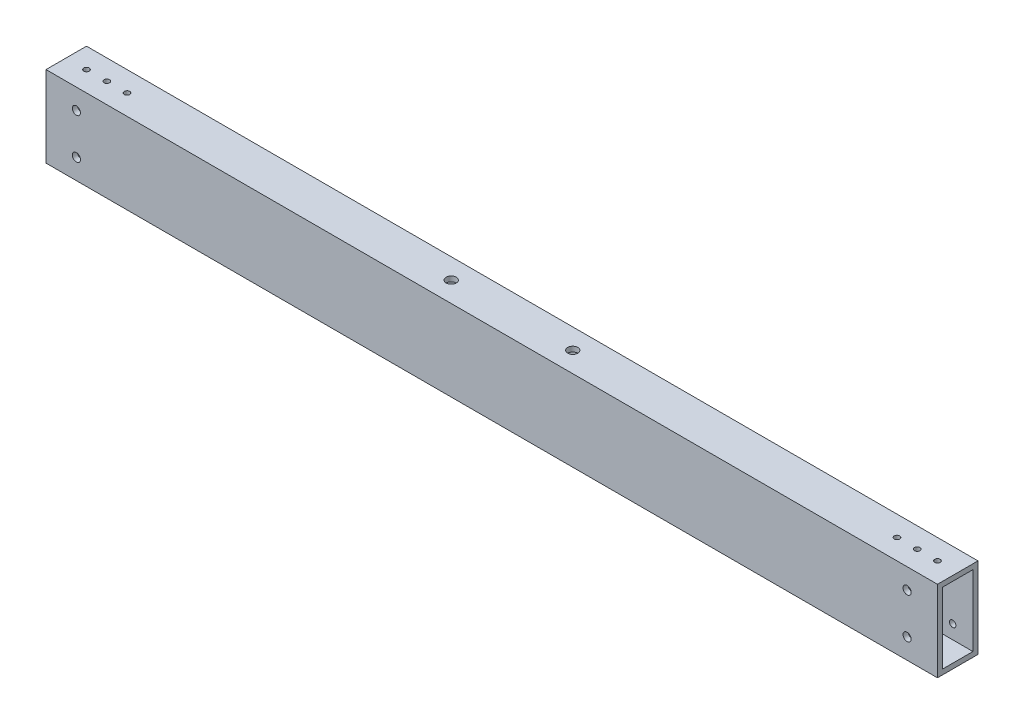
SolidWorks part; units mm, degrees
material "6061-T6 (SS)"
ref_plane "Front Plane" through (0, 0, 0) normal (0, 0, 1) x (1, 0, 0)
ref_plane "Top Plane" through (0, 0, 0) normal (0, 1, 0) x (1, 0, 0)
ref_plane "Right Plane" through (0, 0, 0) normal (1, 0, 0) x (0, 0, -1)
sketch "Sketch1" plane through (0, 0, 0) normal (0, 0, 1) x (1, 0, 0)
  line L1 (-279.4, 25.4) -> (279.4, 25.4)
  line L2 (-279.4, 25.4) -> (-279.4, -25.4)
  line L3 (-279.4, -25.4) -> (279.4, -25.4)
  line L4 (279.4, 25.4) -> (279.4, -25.4)
  line L5 (-279.4, 25.4) -> (279.4, -25.4) construction
  line L6 (-279.4, -25.4) -> (279.4, 25.4) construction
  point P0 (0, 0)
  dimension "D1" = 50.8
  dimension "D2" = 558.8
extrude "Boss-Extrude1" add sketch "Sketch1" along normal mid plane 25.4
sketch "Sketch2" plane through (279.4, 0, 0) normal (1, 0, 0) x (0, 0, -1)
  line L8 (9.525, -22.225) -> (9.525, 22.225)
  line L9 (9.525, 22.225) -> (-9.525, 22.225)
  line L10 (-9.525, 22.225) -> (-9.525, -22.225)
  line L11 (-9.525, -22.225) -> (9.525, -22.225)
  line L12 (9.525, -22.225) -> (9.525, 22.225)
  line L13 (9.525, 22.225) -> (-9.525, 22.225)
  line L14 (-9.525, 22.225) -> (-9.525, -22.225)
  line L15 (-9.525, -22.225) -> (9.525, -22.225)
  dimension "D1" = 3.175
extrude "Cut-Extrude1" cut sketch "Sketch2" against normal through all
sketch "Sketch3" plane through (0, 0, 12.7) normal (0, 0, 1) x (1, 0, 0)
sketch "Sketch4" plane through (0, 25.4, 0) normal (0, 1, 0) x (1, 0, 0)
  line L0 (-279.4, -12.7) -> (-279.4, 12.7) construction
  line L1 (0, -12.7) -> (0, 12.7) construction
  line L2 (279.4, -12.7) -> (-279.4, -12.7) construction
  line L3 (279.4, 12.7) -> (-279.4, 12.7) construction
  circle A0 centre (-304.8, 0) radius 1.7272
  circle A1 centre (-292.1, 0) radius 1.7272
  circle A3 centre (-266.7, 0) radius 1.7272
  circle A4 centre (-254, 0) radius 1.7272
  circle A5 centre (-241.3, 0) radius 1.7272
  circle A7 centre (241.3, 0) radius 1.7272
  circle A8 centre (254, 0) radius 1.7272
  circle A9 centre (266.7, 0) radius 1.7272
  circle A12 centre (-279.4, 0) radius 1.7272 [skipped]
  circle A14 centre (-228.6, 0) radius 1.7272 [skipped]
  dimension "D2" = 3.4544
  dimension "D3" = 7
  dimension "D4" = 12.7
extrude "Cut-Extrude2" cut sketch "Sketch4" against normal blind 6.35
hole_wizard "1/4-20 Tapped Hole1" positions "Sketch8" profile "Sketch7" tap size "1/4-20" standard "ANSI Inch"
sketch "Sketch8" plane through (0, 0, 12.7) normal (0, 0, 1) x (1, 0, 0)
  line L0 (-279.4, 25.4) -> (-279.4, -25.4) construction
  line L1 (279.4, -25.4) -> (279.4, 25.4) construction
  line L2 (-279.4, -25.4) -> (279.4, -25.4) construction
  point P0 (-260.35, 12.7)
  point P2 (-260.35, -12.7)
  point P4 (260.35, 12.7)
  point P6 (260.35, -12.7)
  dimension "D1" = 25.4
  dimension "D2" = 19.05
  dimension "D3" = 25.4
  dimension "D4" = 19.05
  dimension "D5" = 12.7
  dimension "D6" = 12.7
sketch "Sketch7" plane through (-260.35, 12.7, 12.7) normal (1, 0, 0) x (0, -1, 0)
  line L0 (0, 0) -> (0, 6.6138)
  line L1 (0, 6.6138) -> (2.5527, 5.08)
  line L2 (2.5527, 5.08) -> (2.5527, 0)
  line L5 (2.5527, 0) -> (0, 0)
  line L10 (0, 6.6138) -> (-2.5527, 5.08) construction
  line L11 (0, -6.35) -> (0, 107.95) construction
  dimension "Tap Drill Dia." = 5.1054
  dimension "Tap Drill Depth" = 5.08
  dimension "Drill Angle" = 118
hole_wizard "#10-32 Tapped Hole1" positions "Sketch10" profile "Sketch9" tap size "#10-32" standard "ANSI Inch"
sketch "Sketch10" plane through (0, 0, -12.7) normal (0, 0, -1) x (-1, 0, 0)
  line L0 (-279.4, 25.4) -> (279.4, 25.4) construction
  line L1 (-279.4, -25.4) -> (-279.4, 25.4) construction
  point P0 (-266.7, -13.4937)
  point P15 (-190.5, -13.4937)
  point P16 (-114.3, -13.4937)
  point P17 (-38.1, -13.4937)
  point P18 (38.1, -13.4937)
  point P19 (114.3, -13.4937)
  point P20 (190.5, -13.4937)
  point P21 (266.7, -13.4937)
  dimension "D1" = 76.2
  dimension "D2" = 38.8937
  dimension "D3" = 12.7
  dimension "D5" = 8
sketch "Sketch9" plane through (266.7, -13.4937, -12.7) normal (1, 0, 0) x (0, 1, 0)
  line L0 (0, 0) -> (0, 6.2933)
  line L1 (0, 6.2933) -> (2.0193, 5.08)
  line L2 (2.0193, 5.08) -> (2.0193, 0)
  line L5 (2.0193, 0) -> (0, 0)
  line L10 (0, 6.2933) -> (-2.0193, 5.08) construction
  line L11 (0, -6.35) -> (0, 107.95) construction
  dimension "Tap Drill Dia." = 4.0386
  dimension "Tap Drill Depth" = 5.08
  dimension "Drill Angle" = 118
hole_wizard "1/4 (0.25) Diameter Hole1" positions "Sketch12" profile "Sketch11" hole size "1/4" standard "ANSI Inch" end condition through all
sketch "Sketch12" plane through (0, 25.4, 0) normal (0, 1, 0) x (1, 0, 0)
  line L2 (-38.1, 0) -> (38.1, 0) construction
  point P0 (-38.1, 0)
  point P2 (38.1, 0)
  dimension "D1" = 76.2
sketch "Sketch11" plane through (-38.1, 25.4, 0) normal (1, 0, 0) x (0, 0, 1)
  line L0 (0, 0) -> (0, 50.8)
  line L1 (0, 50.8) -> (3.175, 50.8)
  line L2 (3.175, 50.8) -> (3.175, 0)
  line L5 (3.175, 0) -> (0, 0)
  line L11 (0, -6.35) -> (0, 107.95) construction
  dimension "Thru Hole Dia." = 6.35
  dimension "Thru Hole Depth" = 50.8
